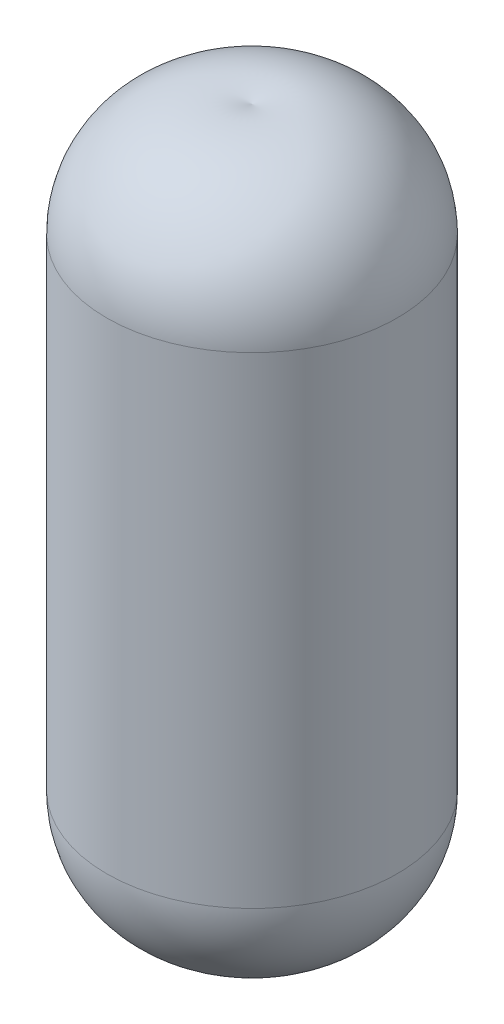
SolidWorks part; units mm, degrees
other "Markup1"
sketch "Sketch2" plane through (1062.5, -500, 1062.5) normal (0.0649, -0.0227, 0.9976) x (-0.9976, -0.0258, 0.0643)
ref_plane "Front Plane" through (0, 0, 0) normal (0, 0, 1) x (1, 0, 0)
ref_plane "Top Plane" through (0, 0, 0) normal (0, 1, 0) x (1, 0, 0)
ref_plane "Right Plane" through (0, 0, 0) normal (1, 0, 0) x (0, 0, -1)
sketch "Sketch1" plane through (0, 0, 0) normal (0, 0, 1) x (1, 0, 0)
  line L0 (0, 1509.902) -> (0, -522.098)
  line L4 (0, -522.098) -> (0, -979.298)
  line L5 (605.79, -509.6402) -> (605.79, 1497.4442)
  line L6 (0, 1509.902) -> (0, 1967.102)
  arc A19 (605.79, -509.6402) -> (0, -979.298) centre (120.8365, -509.6402) cw
  arc A20 (605.79, 1497.4442) -> (0, 1967.102) centre (120.8365, 1497.4442) ccw
  point P0 (0, 0)
  point P10 (0, 493.902)
  dimension "D1" = 605.79
  dimension "D2" = 2032
  dimension "D3" = 1016
  dimension "D4" = 457.2
  dimension "D5" = 457.2
ref_axis "Axis1" through (0, 550, 0) along (0, -1, 0)
revolve "Revolve2" add sketch "Sketch1" angle 360 about axis through (0, 550, 0) along (0, -1, 0)
ref_plane "Plane1" through (0, 493.902, 0) normal (0, 1, 0) x (1, 0, 0)
